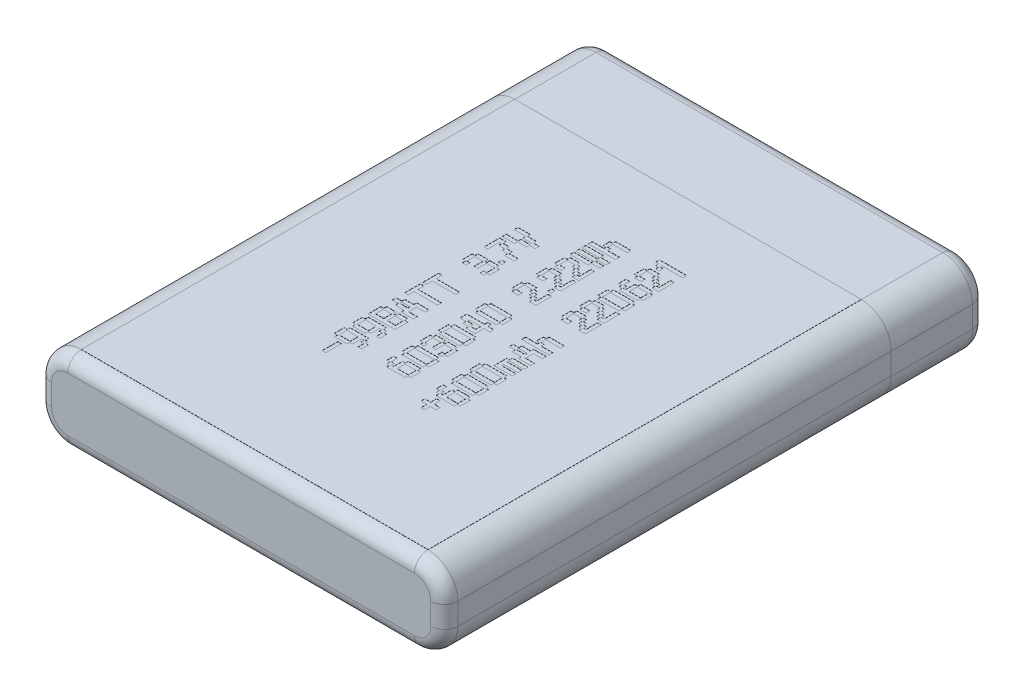
SolidWorks part; units mm, degrees
ref_plane "Front Plane" through (0, 0, 0) normal (0, 0, 1) x (1, 0, 0)
ref_plane "Top Plane" through (0, 0, 0) normal (0, 1, 0) x (1, 0, 0)
ref_plane "Right Plane" through (0, 0, 0) normal (1, 0, 0) x (0, 0, -1)
sketch "Sketch1" plane through (0, 0, 0) normal (0, 1, 0) x (1, 0, 0)
  line L1 (-15, 20) -> (15, 20)
  line L2 (-15, 20) -> (-15, -20)
  line L3 (-15, -20) -> (15, -20)
  line L4 (15, 20) -> (15, -20)
  line L5 (-15, 20) -> (15, -20) construction
  line L6 (-15, -20) -> (15, 20) construction
  point P0 (0, 0)
  dimension "D1" = 40
  dimension "D2" = 30
extrude "Boss-Extrude1" add sketch "Sketch1" along normal blind 6
sketch "Sketch2" plane through (0, 6, 0) normal (0, 1, 0) x (1, 0, 0)
  line L0 (-15, 13) -> (15, 13)
  line L1 (-15, 20) -> (-15, -20) construction
  line L2 (15, -20) -> (15, 20) construction
  line L3 (15, 20) -> (-15, 20) construction
  dimension "D1" = 7
split line "Split Line2"
sketch "Sketch3" plane through (-15, 0, 0) normal (-1, 0, 0) x (0, 0, 1)
  line L0 (-13, 6) -> (-13, 0)
  line L1 (-20, 0) -> (20, 0) construction
split line "Split Line3"
sketch "Sketch4" plane through (0, 0, 0) normal (0, -1, 0) x (-1, 0, 0)
  line L0 (15, 13) -> (-15, 13)
split line "Split Line4"
sketch "Sketch5" plane through (15, 0, 0) normal (1, 0, 0) x (0, 0, -1)
  line L0 (13, 6) -> (13, 0)
split line "Split Line5"
fillet "Fillet1" radius 2.2 8 edges at (-15, 0, -16.5) (-15, 6, -16.5) (15, 0, 3.5) (15, 0, -16.5) (15, 6, -16.5) (15, 6, 3.5) (-15, 0, 3.5) (-15, 6, 3.5)
fillet "Fillet2" radius 1 16 edges at (14.3556, 5.3556, -20) (15, 3, -20) (14.3556, 0.6444, -20) (0, 0, -20) (-14.3556, 0.6444, -20) (-15, 3, -20) (-14.3556, 5.3556, -20) (-14.3556, 5.3556, 20) (-15, 3, 20) (-14.3556, 0.6444, 20) (0, 0, 20) (14.3556, 0.6444, 20) (15, 3, 20) (14.3556, 5.3556, 20) (0, 6, -20) (0, 6, 20)
sketch "Sketch6" plane through (0, 6, 0) normal (0, 1, 0) x (1, 0, 0)
  line L0 (-3.5649, -10.1961) -> (-3.831, -10.1961)
  line L1 (-3.831, -10.1961) -> (-3.831, -9.0385)
  line L2 (-3.831, -9.0385) -> (-3.5649, -9.0385)
  line L3 (-3.5649, -9.0385) -> (-3.5649, -10.1961)
  line L4 (-3.3483, -8.8464) -> (-4.2643, -8.8464)
  line L5 (-4.2643, -8.8464) -> (-4.2643, -8.5562)
  line L6 (-4.2643, -8.5562) -> (-3.3483, -8.5562)
  line L7 (-3.3483, -8.5562) -> (-3.3483, -8.8464)
  line L8 (-3.1317, -8.6298) -> (-3.3974, -8.6298)
  line L9 (-3.3974, -8.6298) -> (-3.3974, -7.9795)
  line L10 (-3.3974, -7.9795) -> (-4.2643, -7.9795)
  line L11 (-4.2643, -7.9795) -> (-4.2643, -7.6888)
  line L12 (-4.2643, -7.6888) -> (-2.9146, -7.6888)
  line L13 (-2.9146, -7.6888) -> (-2.9146, -7.9795)
  line L14 (-2.9146, -7.9795) -> (-3.1317, -7.9795)
  line L15 (-3.1317, -7.9795) -> (-3.1317, -8.6298)
  line L16 (-2.4813, -8.6298) -> (-2.7471, -8.6298)
  line L17 (-2.7471, -8.6298) -> (-2.7471, -8.1225)
  line L18 (-2.7471, -8.1225) -> (-2.4813, -8.1225)
  line L19 (-2.4813, -8.1225) -> (-2.4813, -8.6298)
  line L20 (-4.2152, -8.6298) -> (-4.4813, -8.6298)
  line L21 (-4.4813, -8.6298) -> (-4.4813, -7.9058)
  line L22 (-4.4813, -7.9058) -> (-4.2152, -7.9058)
  line L23 (-4.2152, -7.9058) -> (-4.2152, -8.6298)
  line L24 (-2.698, -8.1961) -> (-2.9637, -8.1961)
  line L25 (-2.9637, -8.1961) -> (-2.9637, -7.9058)
  line L26 (-2.9637, -7.9058) -> (-2.698, -7.9058)
  line L27 (-2.698, -7.9058) -> (-2.698, -8.1961)
  line L28 (-3.3483, -7.4967) -> (-4.2643, -7.4967)
  line L29 (-4.2643, -7.4967) -> (-4.2643, -7.2065)
  line L30 (-4.2643, -7.2065) -> (-3.3483, -7.2065)
  line L31 (-3.3483, -7.2065) -> (-3.3483, -7.4967)
  line L32 (-3.1317, -7.2801) -> (-3.3974, -7.2801)
  line L33 (-3.3974, -7.2801) -> (-3.3974, -6.6298)
  line L34 (-3.3974, -6.6298) -> (-4.2643, -6.6298)
  line L35 (-4.2643, -6.6298) -> (-4.2643, -6.3391)
  line L36 (-4.2643, -6.3391) -> (-2.9146, -6.3391)
  line L37 (-2.9146, -6.3391) -> (-2.9146, -6.6298)
  line L38 (-2.9146, -6.6298) -> (-3.1317, -6.6298)
  line L39 (-3.1317, -6.6298) -> (-3.1317, -7.2801)
  line L40 (-2.4813, -7.2801) -> (-2.7471, -7.2801)
  line L41 (-2.7471, -7.2801) -> (-2.7471, -6.7728)
  line L42 (-2.7471, -6.7728) -> (-2.4813, -6.7728)
  line L43 (-2.4813, -6.7728) -> (-2.4813, -7.2801)
  line L44 (-4.2152, -7.2801) -> (-4.4813, -7.2801)
  line L45 (-4.4813, -7.2801) -> (-4.4813, -6.5562)
  line L46 (-4.4813, -6.5562) -> (-4.2152, -6.5562)
  line L47 (-4.2152, -6.5562) -> (-4.2152, -7.2801)
  line L48 (-2.698, -6.8464) -> (-2.9637, -6.8464)
  line L49 (-2.9637, -6.8464) -> (-2.9637, -6.5562)
  line L50 (-2.9637, -6.5562) -> (-2.698, -6.5562)
  line L51 (-2.698, -6.5562) -> (-2.698, -6.8464)
  line L52 (-2.4813, -6.147) -> (-4.4813, -6.147)
  line L53 (-4.4813, -6.147) -> (-4.4813, -5.2065)
  line L54 (-4.4813, -5.2065) -> (-4.2152, -5.2065)
  line L55 (-4.2152, -5.2065) -> (-4.2152, -5.8568)
  line L56 (-4.2152, -5.8568) -> (-3.614, -5.8568)
  line L57 (-3.614, -5.8568) -> (-3.614, -5.2065)
  line L58 (-3.614, -5.2065) -> (-3.3483, -5.2065)
  line L59 (-3.3483, -5.2065) -> (-3.3483, -5.8568)
  line L60 (-3.3483, -5.8568) -> (-2.7471, -5.8568)
  line L61 (-2.7471, -5.8568) -> (-2.7471, -5.2065)
  line L62 (-2.7471, -5.2065) -> (-2.4813, -5.2065)
  line L63 (-2.4813, -5.2065) -> (-2.4813, -6.147)
  line L64 (-2.698, -5.2801) -> (-3.3974, -5.2801)
  line L65 (-3.3974, -5.2801) -> (-3.3974, -4.9894)
  line L66 (-3.3974, -4.9894) -> (-2.698, -4.9894)
  line L67 (-2.698, -4.9894) -> (-2.698, -5.2801)
  line L68 (-3.5649, -5.2801) -> (-4.2643, -5.2801)
  line L69 (-4.2643, -5.2801) -> (-4.2643, -4.9894)
  line L70 (-4.2643, -4.9894) -> (-3.5649, -4.9894)
  line L71 (-3.5649, -4.9894) -> (-3.5649, -5.2801)
  line L72 (-2.4813, -4.7973) -> (-3.3974, -4.7973)
  line L73 (-3.3974, -4.7973) -> (-3.3974, -4.5807)
  line L74 (-3.3974, -4.5807) -> (-4.0477, -4.5807)
  line L75 (-4.0477, -4.5807) -> (-4.0477, -4.2901)
  line L76 (-4.0477, -4.2901) -> (-3.3974, -4.2901)
  line L77 (-3.3974, -4.2901) -> (-3.3974, -4.147)
  line L78 (-3.3974, -4.147) -> (-4.0477, -4.147)
  line L79 (-4.0477, -4.147) -> (-4.0477, -3.8568)
  line L80 (-4.0477, -3.8568) -> (-3.3974, -3.8568)
  line L81 (-3.3974, -3.8568) -> (-3.3974, -3.6397)
  line L82 (-3.3974, -3.6397) -> (-2.4813, -3.6397)
  line L83 (-2.4813, -3.6397) -> (-2.4813, -3.9304)
  line L84 (-2.4813, -3.9304) -> (-3.1317, -3.9304)
  line L85 (-3.1317, -3.9304) -> (-3.1317, -4.5071)
  line L86 (-3.1317, -4.5071) -> (-2.4813, -4.5071)
  line L87 (-2.4813, -4.5071) -> (-2.4813, -4.7973)
  line L88 (-3.9986, -4.3637) -> (-4.4813, -4.3637)
  line L89 (-4.4813, -4.3637) -> (-4.4813, -4.0734)
  line L90 (-4.4813, -4.0734) -> (-3.9986, -4.0734)
  line L91 (-3.9986, -4.0734) -> (-3.9986, -4.3637)
  line L92 (-4.2152, -3.4476) -> (-4.4813, -3.4476)
  line L93 (-4.4813, -3.4476) -> (-4.4813, -2.2901)
  line L94 (-4.4813, -2.2901) -> (-4.2152, -2.2901)
  line L95 (-4.2152, -2.2901) -> (-4.2152, -2.7237)
  line L96 (-4.2152, -2.7237) -> (-2.4813, -2.7237)
  line L97 (-2.4813, -2.7237) -> (-2.4813, -3.014)
  line L98 (-2.4813, -3.014) -> (-4.2152, -3.014)
  line L99 (-4.2152, -3.014) -> (-4.2152, -3.4476)
  line L100 (-4.2152, -2.0979) -> (-4.4813, -2.0979)
  line L101 (-4.4813, -2.0979) -> (-4.4813, -0.9404)
  line L102 (-4.4813, -0.9404) -> (-4.2152, -0.9404)
  line L103 (-4.2152, -0.9404) -> (-4.2152, -1.374)
  line L104 (-4.2152, -1.374) -> (-2.4813, -1.374)
  line L105 (-2.4813, -1.374) -> (-2.4813, -1.6643)
  line L106 (-2.4813, -1.6643) -> (-4.2152, -1.6643)
  line L107 (-4.2152, -1.6643) -> (-4.2152, -2.0979)
  line L108 (-2.698, 0.6014) -> (-2.9637, 0.6014)
  line L109 (-2.9637, 0.6014) -> (-2.9637, 0.8917)
  line L110 (-2.9637, 0.8917) -> (-2.698, 0.8917)
  line L111 (-2.698, 0.8917) -> (-2.698, 0.6014)
  line L112 (-3.9986, 0.6014) -> (-4.2643, 0.6014)
  line L113 (-4.2643, 0.6014) -> (-4.2643, 0.8917)
  line L114 (-4.2643, 0.8917) -> (-3.9986, 0.8917)
  line L115 (-3.9986, 0.8917) -> (-3.9986, 0.6014)
  line L116 (-2.7471, 0.8181) -> (-2.7471, 1.542)
  line L117 (-2.7471, 1.542) -> (-2.4813, 1.542)
  line L118 (-2.4813, 1.542) -> (-2.4813, 0.8181)
  line L119 (-2.4813, 0.8181) -> (-2.7471, 0.8181)
  line L120 (-3.3483, 0.8181) -> (-3.614, 0.8181)
  line L121 (-3.614, 0.8181) -> (-3.614, 1.542)
  line L122 (-3.614, 1.542) -> (-3.3483, 1.542)
  line L123 (-3.3483, 1.542) -> (-3.3483, 0.8181)
  line L124 (-4.2152, 0.8181) -> (-4.4813, 0.8181)
  line L125 (-4.4813, 0.8181) -> (-4.4813, 1.542)
  line L126 (-4.4813, 1.542) -> (-4.2152, 1.542)
  line L127 (-4.2152, 1.542) -> (-4.2152, 0.8181)
  line L128 (-2.698, 1.4684) -> (-3.3974, 1.4684)
  line L129 (-3.3974, 1.4684) -> (-3.3974, 1.759)
  line L130 (-3.3974, 1.759) -> (-2.698, 1.759)
  line L131 (-2.698, 1.759) -> (-2.698, 1.4684)
  line L132 (-3.5649, 1.4684) -> (-4.2643, 1.4684)
  line L133 (-4.2643, 1.4684) -> (-4.2643, 1.759)
  line L134 (-4.2643, 1.759) -> (-3.5649, 1.759)
  line L135 (-3.5649, 1.759) -> (-3.5649, 1.4684)
  line L136 (-2.698, 1.9511) -> (-2.9637, 1.9511)
  line L137 (-2.9637, 1.9511) -> (-2.9637, 2.2414)
  line L138 (-2.9637, 2.2414) -> (-2.698, 2.2414)
  line L139 (-2.698, 2.2414) -> (-2.698, 1.9511)
  line L140 (-4.2152, 2.4174) -> (-4.4813, 2.4174)
  line L141 (-4.4813, 2.4174) -> (-4.4813, 3.575)
  line L142 (-4.4813, 3.575) -> (-3.9986, 3.575)
  line L143 (-3.9986, 3.575) -> (-3.9986, 3.2843)
  line L144 (-3.9986, 3.2843) -> (-4.2152, 3.2843)
  line L145 (-4.2152, 3.2843) -> (-4.2152, 2.4174)
  line L146 (-3.1807, 2.634) -> (-3.1807, 2.9247)
  line L147 (-3.1807, 2.9247) -> (-2.4813, 2.9247)
  line L148 (-2.4813, 2.9247) -> (-2.4813, 2.634)
  line L149 (-2.4813, 2.634) -> (-3.1807, 2.634)
  line L150 (-3.1317, 2.8511) -> (-3.614, 2.8511)
  line L151 (-3.614, 2.8511) -> (-3.614, 3.1413)
  line L152 (-3.614, 3.1413) -> (-3.1317, 3.1413)
  line L153 (-3.1317, 3.1413) -> (-3.1317, 2.8511)
  line L154 (-3.5649, 3.0677) -> (-4.0477, 3.0677)
  line L155 (-4.0477, 3.0677) -> (-4.0477, 3.358)
  line L156 (-4.0477, 3.358) -> (-3.5649, 3.358)
  line L157 (-3.5649, 3.358) -> (-3.5649, 3.0677)
  line L158 (-3.5649, 3.7671) -> (-4.4813, 3.7671)
  line L159 (-4.4813, 3.7671) -> (-4.4813, 4.0573)
  line L160 (-4.4813, 4.0573) -> (-3.5649, 4.0573)
  line L161 (-3.5649, 4.0573) -> (-3.5649, 3.7671)
  line L162 (-2.9146, 3.9837) -> (-3.614, 3.9837)
  line L163 (-3.614, 3.9837) -> (-3.614, 4.2744)
  line L164 (-3.614, 4.2744) -> (-2.9146, 4.2744)
  line L165 (-2.9146, 4.2744) -> (-2.9146, 3.9837)
  line L166 (-2.9637, 4.2007) -> (-2.9637, 4.491)
  line L167 (-2.9637, 4.491) -> (-2.4813, 4.491)
  line L168 (-2.4813, 4.491) -> (-2.4813, 4.2007)
  line L169 (-2.4813, 4.2007) -> (-2.9637, 4.2007)
  line L170 (-2.9146, 4.4174) -> (-3.614, 4.4174)
  line L171 (-3.614, 4.4174) -> (-3.614, 4.7076)
  line L172 (-3.614, 4.7076) -> (-2.9146, 4.7076)
  line L173 (-2.9146, 4.7076) -> (-2.9146, 4.4174)
  line L174 (-3.5649, 4.634) -> (-4.4813, 4.634)
  line L175 (-4.4813, 4.634) -> (-4.4813, 4.9247)
  line L176 (-4.4813, 4.9247) -> (-3.5649, 4.9247)
  line L177 (-3.5649, 4.9247) -> (-3.5649, 4.634)
  line L178 (0.9523, -8.8464) -> (-0.3974, -8.8464)
  line L179 (-0.3974, -8.8464) -> (-0.3974, -8.5562)
  line L180 (-0.3974, -8.5562) -> (-0.1807, -8.5562)
  line L181 (-0.1807, -8.5562) -> (-0.1807, -7.9058)
  line L182 (-0.1807, -7.9058) -> (0.0854, -7.9058)
  line L183 (0.0854, -7.9058) -> (0.0854, -8.5562)
  line L184 (0.0854, -8.5562) -> (0.9523, -8.5562)
  line L185 (0.9523, -8.5562) -> (0.9523, -8.8464)
  line L186 (0.9032, -8.6298) -> (0.9032, -7.9058)
  line L187 (0.9032, -7.9058) -> (1.169, -7.9058)
  line L188 (1.169, -7.9058) -> (1.169, -8.6298)
  line L189 (1.169, -8.6298) -> (0.9032, -8.6298)
  line L190 (-0.3483, -8.6298) -> (-0.614, -8.6298)
  line L191 (-0.614, -8.6298) -> (-0.614, -8.3391)
  line L192 (-0.614, -8.3391) -> (-0.3483, -8.3391)
  line L193 (-0.3483, -8.3391) -> (-0.3483, -8.6298)
  line L194 (-0.5649, -8.4128) -> (-0.831, -8.4128)
  line L195 (-0.831, -8.4128) -> (-0.831, -7.9058)
  line L196 (-0.831, -7.9058) -> (-0.5649, -7.9058)
  line L197 (-0.5649, -7.9058) -> (-0.5649, -8.4128)
  line L198 (0.9523, -7.9795) -> (0.0363, -7.9795)
  line L199 (0.0363, -7.9795) -> (0.0363, -7.6888)
  line L200 (0.0363, -7.6888) -> (0.9523, -7.6888)
  line L201 (0.9523, -7.6888) -> (0.9523, -7.9795)
  line L202 (0.9523, -7.4967) -> (-0.614, -7.4967)
  line L203 (-0.614, -7.4967) -> (-0.614, -7.2065)
  line L204 (-0.614, -7.2065) -> (0.9523, -7.2065)
  line L205 (0.9523, -7.2065) -> (0.9523, -7.4967)
  line L206 (0.9032, -6.5562) -> (1.169, -6.5562)
  line L207 (1.169, -6.5562) -> (1.169, -7.2801)
  line L208 (1.169, -7.2801) -> (0.9032, -7.2801)
  line L209 (0.9032, -7.2801) -> (0.9032, -6.5562)
  line L210 (-0.614, -6.6298) -> (-0.614, -6.3391)
  line L211 (-0.614, -6.3391) -> (0.9523, -6.3391)
  line L212 (0.9523, -6.3391) -> (0.9523, -6.6298)
  line L213 (0.9523, -6.6298) -> (-0.614, -6.6298)
  line L214 (-0.831, -6.5562) -> (-0.5649, -6.5562)
  line L215 (-0.5649, -6.5562) -> (-0.5649, -7.2801)
  line L216 (-0.5649, -7.2801) -> (-0.831, -7.2801)
  line L217 (-0.831, -7.2801) -> (-0.831, -6.5562)
  line L218 (0.9523, -6.147) -> (0.6866, -6.147)
  line L219 (0.6866, -6.147) -> (0.6866, -5.8568)
  line L220 (0.6866, -5.8568) -> (0.9523, -5.8568)
  line L221 (0.9523, -5.8568) -> (0.9523, -6.147)
  line L222 (-0.3483, -6.147) -> (-0.614, -6.147)
  line L223 (-0.614, -6.147) -> (-0.614, -5.8568)
  line L224 (-0.614, -5.8568) -> (-0.3483, -5.8568)
  line L225 (-0.3483, -5.8568) -> (-0.3483, -6.147)
  line L226 (0.9032, -5.9304) -> (0.9032, -5.2065)
  line L227 (0.9032, -5.2065) -> (1.169, -5.2065)
  line L228 (1.169, -5.2065) -> (1.169, -5.9304)
  line L229 (1.169, -5.9304) -> (0.9032, -5.9304)
  line L230 (0.302, -5.9304) -> (0.0363, -5.9304)
  line L231 (0.0363, -5.9304) -> (0.0363, -5.2065)
  line L232 (0.0363, -5.2065) -> (0.302, -5.2065)
  line L233 (0.302, -5.2065) -> (0.302, -5.9304)
  line L234 (-0.5649, -5.9304) -> (-0.831, -5.9304)
  line L235 (-0.831, -5.9304) -> (-0.831, -5.2065)
  line L236 (-0.831, -5.2065) -> (-0.5649, -5.2065)
  line L237 (-0.5649, -5.2065) -> (-0.5649, -5.9304)
  line L238 (0.9523, -5.2801) -> (0.2529, -5.2801)
  line L239 (0.2529, -5.2801) -> (0.2529, -4.9894)
  line L240 (0.2529, -4.9894) -> (0.9523, -4.9894)
  line L241 (0.9523, -4.9894) -> (0.9523, -5.2801)
  line L242 (0.0854, -5.2801) -> (-0.614, -5.2801)
  line L243 (-0.614, -5.2801) -> (-0.614, -4.9894)
  line L244 (-0.614, -4.9894) -> (0.0854, -4.9894)
  line L245 (0.0854, -4.9894) -> (0.0854, -5.2801)
  line L246 (0.9523, -4.7973) -> (-0.614, -4.7973)
  line L247 (-0.614, -4.7973) -> (-0.614, -4.5071)
  line L248 (-0.614, -4.5071) -> (0.9523, -4.5071)
  line L249 (0.9523, -4.5071) -> (0.9523, -4.7973)
  line L250 (0.9032, -3.8568) -> (1.169, -3.8568)
  line L251 (1.169, -3.8568) -> (1.169, -4.5807)
  line L252 (1.169, -4.5807) -> (0.9032, -4.5807)
  line L253 (0.9032, -4.5807) -> (0.9032, -3.8568)
  line L254 (-0.614, -3.9304) -> (-0.614, -3.6397)
  line L255 (-0.614, -3.6397) -> (0.9523, -3.6397)
  line L256 (0.9523, -3.6397) -> (0.9523, -3.9304)
  line L257 (0.9523, -3.9304) -> (-0.614, -3.9304)
  line L258 (-0.831, -3.8568) -> (-0.5649, -3.8568)
  line L259 (-0.5649, -3.8568) -> (-0.5649, -4.5807)
  line L260 (-0.5649, -4.5807) -> (-0.831, -4.5807)
  line L261 (-0.831, -4.5807) -> (-0.831, -3.8568)
  line L262 (0.7357, -3.4476) -> (0.0363, -3.4476)
  line L263 (0.0363, -3.4476) -> (0.0363, -3.1574)
  line L264 (0.0363, -3.1574) -> (0.4696, -3.1574)
  line L265 (0.4696, -3.1574) -> (0.4696, -2.7973)
  line L266 (0.4696, -2.7973) -> (-0.3483, -2.7973)
  line L267 (-0.3483, -2.7973) -> (-0.3483, -3.014)
  line L268 (-0.3483, -3.014) -> (-0.831, -3.014)
  line L269 (-0.831, -3.014) -> (-0.831, -2.5071)
  line L270 (-0.831, -2.5071) -> (0.4696, -2.5071)
  line L271 (0.4696, -2.5071) -> (0.4696, -2.2901)
  line L272 (0.4696, -2.2901) -> (0.7357, -2.2901)
  line L273 (0.7357, -2.2901) -> (0.7357, -2.5071)
  line L274 (0.7357, -2.5071) -> (1.169, -2.5071)
  line L275 (1.169, -2.5071) -> (1.169, -2.7973)
  line L276 (1.169, -2.7973) -> (0.7357, -2.7973)
  line L277 (0.7357, -2.7973) -> (0.7357, -3.4476)
  line L278 (0.0854, -3.231) -> (-0.3974, -3.231)
  line L279 (-0.3974, -3.231) -> (-0.3974, -2.9404)
  line L280 (-0.3974, -2.9404) -> (0.0854, -2.9404)
  line L281 (0.0854, -2.9404) -> (0.0854, -3.231)
  line L282 (0.9523, -2.0979) -> (-0.614, -2.0979)
  line L283 (-0.614, -2.0979) -> (-0.614, -1.8077)
  line L284 (-0.614, -1.8077) -> (0.9523, -1.8077)
  line L285 (0.9523, -1.8077) -> (0.9523, -2.0979)
  line L286 (0.9032, -1.1574) -> (1.169, -1.1574)
  line L287 (1.169, -1.1574) -> (1.169, -1.8813)
  line L288 (1.169, -1.8813) -> (0.9032, -1.8813)
  line L289 (0.9032, -1.8813) -> (0.9032, -1.1574)
  line L290 (-0.614, -1.231) -> (-0.614, -0.9404)
  line L291 (-0.614, -0.9404) -> (0.9523, -0.9404)
  line L292 (0.9523, -0.9404) -> (0.9523, -1.231)
  line L293 (0.9523, -1.231) -> (-0.614, -1.231)
  line L294 (-0.831, -1.1574) -> (-0.5649, -1.1574)
  line L295 (-0.5649, -1.1574) -> (-0.5649, -1.8813)
  line L296 (-0.5649, -1.8813) -> (-0.831, -1.8813)
  line L297 (-0.831, -1.8813) -> (-0.831, -1.1574)
  line L298 (0.6866, 0.6014) -> (0.6866, 0.8917)
  line L299 (0.6866, 0.8917) -> (0.9032, 0.8917)
  line L300 (0.9032, 0.8917) -> (0.9032, 1.759)
  line L301 (0.9032, 1.759) -> (1.169, 1.759)
  line L302 (1.169, 1.759) -> (1.169, 0.6014)
  line L303 (1.169, 0.6014) -> (0.6866, 0.6014)
  line L304 (-0.1317, 0.6014) -> (-0.614, 0.6014)
  line L305 (-0.614, 0.6014) -> (-0.614, 0.8917)
  line L306 (-0.614, 0.8917) -> (-0.1317, 0.8917)
  line L307 (-0.1317, 0.8917) -> (-0.1317, 0.6014)
  line L308 (0.7357, 0.8181) -> (0.4696, 0.8181)
  line L309 (0.4696, 0.8181) -> (0.4696, 1.1087)
  line L310 (0.4696, 1.1087) -> (0.7357, 1.1087)
  line L311 (0.7357, 1.1087) -> (0.7357, 0.8181)
  line L312 (-0.5649, 0.8181) -> (-0.831, 0.8181)
  line L313 (-0.831, 0.8181) -> (-0.831, 1.542)
  line L314 (-0.831, 1.542) -> (-0.5649, 1.542)
  line L315 (-0.5649, 1.542) -> (-0.5649, 0.8181)
  line L316 (0.5187, 1.0351) -> (0.2529, 1.0351)
  line L317 (0.2529, 1.0351) -> (0.2529, 1.3254)
  line L318 (0.2529, 1.3254) -> (0.5187, 1.3254)
  line L319 (0.5187, 1.3254) -> (0.5187, 1.0351)
  line L320 (0.302, 1.2517) -> (0.0363, 1.2517)
  line L321 (0.0363, 1.2517) -> (0.0363, 1.542)
  line L322 (0.0363, 1.542) -> (0.302, 1.542)
  line L323 (0.302, 1.542) -> (0.302, 1.2517)
  line L324 (0.0854, 1.4684) -> (-0.614, 1.4684)
  line L325 (-0.614, 1.4684) -> (-0.614, 1.759)
  line L326 (-0.614, 1.759) -> (0.0854, 1.759)
  line L327 (0.0854, 1.759) -> (0.0854, 1.4684)
  line L328 (0.9523, 1.9511) -> (0.6866, 1.9511)
  line L329 (0.6866, 1.9511) -> (0.6866, 2.2414)
  line L330 (0.6866, 2.2414) -> (0.9523, 2.2414)
  line L331 (0.9523, 2.2414) -> (0.9523, 1.9511)
  line L332 (0.6866, 2.4174) -> (0.6866, 2.7076)
  line L333 (0.6866, 2.7076) -> (0.9032, 2.7076)
  line L334 (0.9032, 2.7076) -> (0.9032, 3.575)
  line L335 (0.9032, 3.575) -> (1.169, 3.575)
  line L336 (1.169, 3.575) -> (1.169, 2.4174)
  line L337 (1.169, 2.4174) -> (0.6866, 2.4174)
  line L338 (-0.1317, 2.4174) -> (-0.614, 2.4174)
  line L339 (-0.614, 2.4174) -> (-0.614, 2.7076)
  line L340 (-0.614, 2.7076) -> (-0.1317, 2.7076)
  line L341 (-0.1317, 2.7076) -> (-0.1317, 2.4174)
  line L342 (0.7357, 2.634) -> (0.4696, 2.634)
  line L343 (0.4696, 2.634) -> (0.4696, 2.9247)
  line L344 (0.4696, 2.9247) -> (0.7357, 2.9247)
  line L345 (0.7357, 2.9247) -> (0.7357, 2.634)
  line L346 (-0.5649, 2.634) -> (-0.831, 2.634)
  line L347 (-0.831, 2.634) -> (-0.831, 3.358)
  line L348 (-0.831, 3.358) -> (-0.5649, 3.358)
  line L349 (-0.5649, 3.358) -> (-0.5649, 2.634)
  line L350 (0.5187, 2.8511) -> (0.2529, 2.8511)
  line L351 (0.2529, 2.8511) -> (0.2529, 3.1413)
  line L352 (0.2529, 3.1413) -> (0.5187, 3.1413)
  line L353 (0.5187, 3.1413) -> (0.5187, 2.8511)
  line L354 (0.302, 3.0677) -> (0.0363, 3.0677)
  line L355 (0.0363, 3.0677) -> (0.0363, 3.358)
  line L356 (0.0363, 3.358) -> (0.302, 3.358)
  line L357 (0.302, 3.358) -> (0.302, 3.0677)
  line L358 (0.0854, 3.2843) -> (-0.614, 3.2843)
  line L359 (-0.614, 3.2843) -> (-0.614, 3.575)
  line L360 (-0.614, 3.575) -> (0.0854, 3.575)
  line L361 (0.0854, 3.575) -> (0.0854, 3.2843)
  line L362 (0.6866, 3.7671) -> (0.6866, 4.0573)
  line L363 (0.6866, 4.0573) -> (0.9032, 4.0573)
  line L364 (0.9032, 4.0573) -> (0.9032, 4.9247)
  line L365 (0.9032, 4.9247) -> (1.169, 4.9247)
  line L366 (1.169, 4.9247) -> (1.169, 3.7671)
  line L367 (1.169, 3.7671) -> (0.6866, 3.7671)
  line L368 (-0.1317, 3.7671) -> (-0.614, 3.7671)
  line L369 (-0.614, 3.7671) -> (-0.614, 4.0573)
  line L370 (-0.614, 4.0573) -> (-0.1317, 4.0573)
  line L371 (-0.1317, 4.0573) -> (-0.1317, 3.7671)
  line L372 (0.7357, 3.9837) -> (0.4696, 3.9837)
  line L373 (0.4696, 3.9837) -> (0.4696, 4.2744)
  line L374 (0.4696, 4.2744) -> (0.7357, 4.2744)
  line L375 (0.7357, 4.2744) -> (0.7357, 3.9837)
  line L376 (-0.5649, 3.9837) -> (-0.831, 3.9837)
  line L377 (-0.831, 3.9837) -> (-0.831, 4.7076)
  line L378 (-0.831, 4.7076) -> (-0.5649, 4.7076)
  line L379 (-0.5649, 4.7076) -> (-0.5649, 3.9837)
  line L380 (0.5187, 4.2007) -> (0.2529, 4.2007)
  line L381 (0.2529, 4.2007) -> (0.2529, 4.491)
  line L382 (0.2529, 4.491) -> (0.5187, 4.491)
  line L383 (0.5187, 4.491) -> (0.5187, 4.2007)
  line L384 (0.302, 4.4174) -> (0.0363, 4.4174)
  line L385 (0.0363, 4.4174) -> (0.0363, 4.7076)
  line L386 (0.0363, 4.7076) -> (0.302, 4.7076)
  line L387 (0.302, 4.7076) -> (0.302, 4.4174)
  line L388 (0.0854, 4.634) -> (-0.614, 4.634)
  line L389 (-0.614, 4.634) -> (-0.614, 4.9247)
  line L390 (-0.614, 4.9247) -> (0.0854, 4.9247)
  line L391 (0.0854, 4.9247) -> (0.0854, 4.634)
  line L392 (0.5187, 5.1168) -> (-0.831, 5.1168)
  line L393 (-0.831, 5.1168) -> (-0.831, 5.407)
  line L394 (-0.831, 5.407) -> (0.5187, 5.407)
  line L395 (0.5187, 5.407) -> (0.5187, 5.1168)
  line L396 (0.4696, 5.3334) -> (0.4696, 5.6241)
  line L397 (0.4696, 5.6241) -> (1.169, 5.6241)
  line L398 (1.169, 5.6241) -> (1.169, 5.3334)
  line L399 (1.169, 5.3334) -> (0.4696, 5.3334)
  line L400 (0.5187, 5.5504) -> (-0.831, 5.5504)
  line L401 (-0.831, 5.5504) -> (-0.831, 5.8407)
  line L402 (-0.831, 5.8407) -> (0.5187, 5.8407)
  line L403 (0.5187, 5.8407) -> (0.5187, 5.5504)
  line L404 (0.4696, 5.7671) -> (0.4696, 6.0573)
  line L405 (0.4696, 6.0573) -> (1.169, 6.0573)
  line L406 (1.169, 6.0573) -> (1.169, 5.7671)
  line L407 (1.169, 5.7671) -> (0.4696, 5.7671)
  line L408 (0.5187, 5.9837) -> (-0.831, 5.9837)
  line L409 (-0.831, 5.9837) -> (-0.831, 6.2744)
  line L410 (-0.831, 6.2744) -> (0.5187, 6.2744)
  line L411 (0.5187, 6.2744) -> (0.5187, 5.9837)
  line L412 (1.169, 6.4665) -> (-0.831, 6.4665)
  line L413 (-0.831, 6.4665) -> (-0.831, 6.7567)
  line L414 (-0.831, 6.7567) -> (0.0363, 6.7567)
  line L415 (0.0363, 6.7567) -> (0.0363, 6.9738)
  line L416 (0.0363, 6.9738) -> (0.302, 6.9738)
  line L417 (0.302, 6.9738) -> (0.302, 6.7567)
  line L418 (0.302, 6.7567) -> (1.169, 6.7567)
  line L419 (1.169, 6.7567) -> (1.169, 6.4665)
  line L420 (0.0854, 6.9001) -> (-0.1807, 6.9001)
  line L421 (-0.1807, 6.9001) -> (-0.1807, 7.407)
  line L422 (-0.1807, 7.407) -> (0.0854, 7.407)
  line L423 (0.0854, 7.407) -> (0.0854, 6.9001)
  line L424 (1.169, 7.3334) -> (0.0363, 7.3334)
  line L425 (0.0363, 7.3334) -> (0.0363, 7.6241)
  line L426 (0.0363, 7.6241) -> (1.169, 7.6241)
  line L427 (1.169, 7.6241) -> (1.169, 7.3334)
  line L428 (3.7357, -10.1961) -> (3.4696, -10.1961)
  line L429 (3.4696, -10.1961) -> (3.4696, -9.7624)
  line L430 (3.4696, -9.7624) -> (3.0363, -9.7624)
  line L431 (3.0363, -9.7624) -> (3.0363, -9.4722)
  line L432 (3.0363, -9.4722) -> (3.4696, -9.4722)
  line L433 (3.4696, -9.4722) -> (3.4696, -9.0385)
  line L434 (3.4696, -9.0385) -> (3.7357, -9.0385)
  line L435 (3.7357, -9.0385) -> (3.7357, -9.4722)
  line L436 (3.7357, -9.4722) -> (4.169, -9.4722)
  line L437 (4.169, -9.4722) -> (4.169, -9.7624)
  line L438 (4.169, -9.7624) -> (3.7357, -9.7624)
  line L439 (3.7357, -9.7624) -> (3.7357, -10.1961)
  line L440 (4.6026, -8.8464) -> (3.2529, -8.8464)
  line L441 (3.2529, -8.8464) -> (3.2529, -8.5562)
  line L442 (3.2529, -8.5562) -> (3.4696, -8.5562)
  line L443 (3.4696, -8.5562) -> (3.4696, -7.9058)
  line L444 (3.4696, -7.9058) -> (3.7357, -7.9058)
  line L445 (3.7357, -7.9058) -> (3.7357, -8.5562)
  line L446 (3.7357, -8.5562) -> (4.6026, -8.5562)
  line L447 (4.6026, -8.5562) -> (4.6026, -8.8464)
  line L448 (4.5535, -8.6298) -> (4.5535, -7.9058)
  line L449 (4.5535, -7.9058) -> (4.8193, -7.9058)
  line L450 (4.8193, -7.9058) -> (4.8193, -8.6298)
  line L451 (4.8193, -8.6298) -> (4.5535, -8.6298)
  line L452 (3.302, -8.6298) -> (3.0363, -8.6298)
  line L453 (3.0363, -8.6298) -> (3.0363, -8.3391)
  line L454 (3.0363, -8.3391) -> (3.302, -8.3391)
  line L455 (3.302, -8.3391) -> (3.302, -8.6298)
  line L456 (3.0854, -8.4128) -> (2.8193, -8.4128)
  line L457 (2.8193, -8.4128) -> (2.8193, -7.9058)
  line L458 (2.8193, -7.9058) -> (3.0854, -7.9058)
  line L459 (3.0854, -7.9058) -> (3.0854, -8.4128)
  line L460 (4.6026, -7.9795) -> (3.6866, -7.9795)
  line L461 (3.6866, -7.9795) -> (3.6866, -7.6888)
  line L462 (3.6866, -7.6888) -> (4.6026, -7.6888)
  line L463 (4.6026, -7.6888) -> (4.6026, -7.9795)
  line L464 (4.6026, -7.4967) -> (3.0363, -7.4967)
  line L465 (3.0363, -7.4967) -> (3.0363, -7.2065)
  line L466 (3.0363, -7.2065) -> (4.6026, -7.2065)
  line L467 (4.6026, -7.2065) -> (4.6026, -7.4967)
  line L468 (4.5535, -6.5562) -> (4.8193, -6.5562)
  line L469 (4.8193, -6.5562) -> (4.8193, -7.2801)
  line L470 (4.8193, -7.2801) -> (4.5535, -7.2801)
  line L471 (4.5535, -7.2801) -> (4.5535, -6.5562)
  line L472 (3.0363, -6.6298) -> (3.0363, -6.3391)
  line L473 (3.0363, -6.3391) -> (4.6026, -6.3391)
  line L474 (4.6026, -6.3391) -> (4.6026, -6.6298)
  line L475 (4.6026, -6.6298) -> (3.0363, -6.6298)
  line L476 (2.8193, -6.5562) -> (3.0854, -6.5562)
  line L477 (3.0854, -6.5562) -> (3.0854, -7.2801)
  line L478 (3.0854, -7.2801) -> (2.8193, -7.2801)
  line L479 (2.8193, -7.2801) -> (2.8193, -6.5562)
  line L480 (4.6026, -6.147) -> (3.0363, -6.147)
  line L481 (3.0363, -6.147) -> (3.0363, -5.8568)
  line L482 (3.0363, -5.8568) -> (4.6026, -5.8568)
  line L483 (4.6026, -5.8568) -> (4.6026, -6.147)
  line L484 (4.5535, -5.2065) -> (4.8193, -5.2065)
  line L485 (4.8193, -5.2065) -> (4.8193, -5.9304)
  line L486 (4.8193, -5.9304) -> (4.5535, -5.9304)
  line L487 (4.5535, -5.9304) -> (4.5535, -5.2065)
  line L488 (3.0363, -5.2801) -> (3.0363, -4.9894)
  line L489 (3.0363, -4.9894) -> (4.6026, -4.9894)
  line L490 (4.6026, -4.9894) -> (4.6026, -5.2801)
  line L491 (4.6026, -5.2801) -> (3.0363, -5.2801)
  line L492 (2.8193, -5.2065) -> (3.0854, -5.2065)
  line L493 (3.0854, -5.2065) -> (3.0854, -5.9304)
  line L494 (3.0854, -5.9304) -> (2.8193, -5.9304)
  line L495 (2.8193, -5.9304) -> (2.8193, -5.2065)
  line L496 (4.8193, -4.7973) -> (3.4696, -4.7973)
  line L497 (3.4696, -4.7973) -> (3.4696, -3.8568)
  line L498 (3.4696, -3.8568) -> (3.7357, -3.8568)
  line L499 (3.7357, -3.8568) -> (3.7357, -4.0734)
  line L500 (3.7357, -4.0734) -> (4.8193, -4.0734)
  line L501 (4.8193, -4.0734) -> (4.8193, -4.3637)
  line L502 (4.8193, -4.3637) -> (3.7357, -4.3637)
  line L503 (3.7357, -4.3637) -> (3.7357, -4.5071)
  line L504 (3.7357, -4.5071) -> (4.8193, -4.5071)
  line L505 (4.8193, -4.5071) -> (4.8193, -4.7973)
  line L506 (4.8193, -3.9304) -> (3.6866, -3.9304)
  line L507 (3.6866, -3.9304) -> (3.6866, -3.6397)
  line L508 (3.6866, -3.6397) -> (4.8193, -3.6397)
  line L509 (4.8193, -3.6397) -> (4.8193, -3.9304)
  line L510 (4.8193, -3.4476) -> (3.9032, -3.4476)
  line L511 (3.9032, -3.4476) -> (3.9032, -3.231)
  line L512 (3.9032, -3.231) -> (3.2529, -3.231)
  line L513 (3.2529, -3.231) -> (3.2529, -2.9404)
  line L514 (3.2529, -2.9404) -> (3.9032, -2.9404)
  line L515 (3.9032, -2.9404) -> (3.9032, -2.7973)
  line L516 (3.9032, -2.7973) -> (3.2529, -2.7973)
  line L517 (3.2529, -2.7973) -> (3.2529, -2.5071)
  line L518 (3.2529, -2.5071) -> (3.9032, -2.5071)
  line L519 (3.9032, -2.5071) -> (3.9032, -2.2901)
  line L520 (3.9032, -2.2901) -> (4.8193, -2.2901)
  line L521 (4.8193, -2.2901) -> (4.8193, -2.5807)
  line L522 (4.8193, -2.5807) -> (4.169, -2.5807)
  line L523 (4.169, -2.5807) -> (4.169, -3.1574)
  line L524 (4.169, -3.1574) -> (4.8193, -3.1574)
  line L525 (4.8193, -3.1574) -> (4.8193, -3.4476)
  line L526 (3.302, -3.014) -> (2.8193, -3.014)
  line L527 (2.8193, -3.014) -> (2.8193, -2.7237)
  line L528 (2.8193, -2.7237) -> (3.302, -2.7237)
  line L529 (3.302, -2.7237) -> (3.302, -3.014)
  line L530 (4.8193, -2.0979) -> (2.8193, -2.0979)
  line L531 (2.8193, -2.0979) -> (2.8193, -1.8077)
  line L532 (2.8193, -1.8077) -> (3.6866, -1.8077)
  line L533 (3.6866, -1.8077) -> (3.6866, -1.5907)
  line L534 (3.6866, -1.5907) -> (3.9523, -1.5907)
  line L535 (3.9523, -1.5907) -> (3.9523, -1.8077)
  line L536 (3.9523, -1.8077) -> (4.8193, -1.8077)
  line L537 (4.8193, -1.8077) -> (4.8193, -2.0979)
  line L538 (3.7357, -1.6643) -> (3.4696, -1.6643)
  line L539 (3.4696, -1.6643) -> (3.4696, -1.1574)
  line L540 (3.4696, -1.1574) -> (3.7357, -1.1574)
  line L541 (3.7357, -1.1574) -> (3.7357, -1.6643)
  line L542 (4.8193, -1.231) -> (3.6866, -1.231)
  line L543 (3.6866, -1.231) -> (3.6866, -0.9404)
  line L544 (3.6866, -0.9404) -> (4.8193, -0.9404)
  line L545 (4.8193, -0.9404) -> (4.8193, -1.231)
  line L546 (4.3369, 0.6014) -> (4.3369, 0.8917)
  line L547 (4.3369, 0.8917) -> (4.5535, 0.8917)
  line L548 (4.5535, 0.8917) -> (4.5535, 1.759)
  line L549 (4.5535, 1.759) -> (4.8193, 1.759)
  line L550 (4.8193, 1.759) -> (4.8193, 0.6014)
  line L551 (4.8193, 0.6014) -> (4.3369, 0.6014)
  line L552 (3.5187, 0.6014) -> (3.0363, 0.6014)
  line L553 (3.0363, 0.6014) -> (3.0363, 0.8917)
  line L554 (3.0363, 0.8917) -> (3.5187, 0.8917)
  line L555 (3.5187, 0.8917) -> (3.5187, 0.6014)
  line L556 (4.386, 0.8181) -> (4.1199, 0.8181)
  line L557 (4.1199, 0.8181) -> (4.1199, 1.1087)
  line L558 (4.1199, 1.1087) -> (4.386, 1.1087)
  line L559 (4.386, 1.1087) -> (4.386, 0.8181)
  line L560 (3.0854, 0.8181) -> (2.8193, 0.8181)
  line L561 (2.8193, 0.8181) -> (2.8193, 1.542)
  line L562 (2.8193, 1.542) -> (3.0854, 1.542)
  line L563 (3.0854, 1.542) -> (3.0854, 0.8181)
  line L564 (4.169, 1.0351) -> (3.9032, 1.0351)
  line L565 (3.9032, 1.0351) -> (3.9032, 1.3254)
  line L566 (3.9032, 1.3254) -> (4.169, 1.3254)
  line L567 (4.169, 1.3254) -> (4.169, 1.0351)
  line L568 (3.9523, 1.2517) -> (3.6866, 1.2517)
  line L569 (3.6866, 1.2517) -> (3.6866, 1.542)
  line L570 (3.6866, 1.542) -> (3.9523, 1.542)
  line L571 (3.9523, 1.542) -> (3.9523, 1.2517)
  line L572 (3.7357, 1.4684) -> (3.0363, 1.4684)
  line L573 (3.0363, 1.4684) -> (3.0363, 1.759)
  line L574 (3.0363, 1.759) -> (3.7357, 1.759)
  line L575 (3.7357, 1.759) -> (3.7357, 1.4684)
  line L576 (4.3369, 1.9511) -> (4.3369, 2.2414)
  line L577 (4.3369, 2.2414) -> (4.5535, 2.2414)
  line L578 (4.5535, 2.2414) -> (4.5535, 3.1087)
  line L579 (4.5535, 3.1087) -> (4.8193, 3.1087)
  line L580 (4.8193, 3.1087) -> (4.8193, 1.9511)
  line L581 (4.8193, 1.9511) -> (4.3369, 1.9511)
  line L582 (3.5187, 1.9511) -> (3.0363, 1.9511)
  line L583 (3.0363, 1.9511) -> (3.0363, 2.2414)
  line L584 (3.0363, 2.2414) -> (3.5187, 2.2414)
  line L585 (3.5187, 2.2414) -> (3.5187, 1.9511)
  line L586 (4.386, 2.1678) -> (4.1199, 2.1678)
  line L587 (4.1199, 2.1678) -> (4.1199, 2.4584)
  line L588 (4.1199, 2.4584) -> (4.386, 2.4584)
  line L589 (4.386, 2.4584) -> (4.386, 2.1678)
  line L590 (3.0854, 2.1678) -> (2.8193, 2.1678)
  line L591 (2.8193, 2.1678) -> (2.8193, 2.8917)
  line L592 (2.8193, 2.8917) -> (3.0854, 2.8917)
  line L593 (3.0854, 2.8917) -> (3.0854, 2.1678)
  line L594 (4.169, 2.3848) -> (3.9032, 2.3848)
  line L595 (3.9032, 2.3848) -> (3.9032, 2.6751)
  line L596 (3.9032, 2.6751) -> (4.169, 2.6751)
  line L597 (4.169, 2.6751) -> (4.169, 2.3848)
  line L598 (3.9523, 2.6014) -> (3.6866, 2.6014)
  line L599 (3.6866, 2.6014) -> (3.6866, 2.8917)
  line L600 (3.6866, 2.8917) -> (3.9523, 2.8917)
  line L601 (3.9523, 2.8917) -> (3.9523, 2.6014)
  line L602 (3.7357, 2.8181) -> (3.0363, 2.8181)
  line L603 (3.0363, 2.8181) -> (3.0363, 3.1087)
  line L604 (3.0363, 3.1087) -> (3.7357, 3.1087)
  line L605 (3.7357, 3.1087) -> (3.7357, 2.8181)
  line L606 (4.6026, 3.3008) -> (3.0363, 3.3008)
  line L607 (3.0363, 3.3008) -> (3.0363, 3.5911)
  line L608 (3.0363, 3.5911) -> (4.6026, 3.5911)
  line L609 (4.6026, 3.5911) -> (4.6026, 3.3008)
  line L610 (4.5535, 4.2414) -> (4.8193, 4.2414)
  line L611 (4.8193, 4.2414) -> (4.8193, 3.5175)
  line L612 (4.8193, 3.5175) -> (4.5535, 3.5175)
  line L613 (4.5535, 3.5175) -> (4.5535, 4.2414)
  line L614 (3.0363, 4.1678) -> (3.0363, 4.4584)
  line L615 (3.0363, 4.4584) -> (4.6026, 4.4584)
  line L616 (4.6026, 4.4584) -> (4.6026, 4.1678)
  line L617 (4.6026, 4.1678) -> (3.0363, 4.1678)
  line L618 (2.8193, 4.2414) -> (3.0854, 4.2414)
  line L619 (3.0854, 4.2414) -> (3.0854, 3.5175)
  line L620 (3.0854, 3.5175) -> (2.8193, 3.5175)
  line L621 (2.8193, 3.5175) -> (2.8193, 4.2414)
  line L622 (4.6026, 4.6505) -> (3.2529, 4.6505)
  line L623 (3.2529, 4.6505) -> (3.2529, 4.9408)
  line L624 (3.2529, 4.9408) -> (3.4696, 4.9408)
  line L625 (3.4696, 4.9408) -> (3.4696, 5.5911)
  line L626 (3.4696, 5.5911) -> (3.7357, 5.5911)
  line L627 (3.7357, 5.5911) -> (3.7357, 4.9408)
  line L628 (3.7357, 4.9408) -> (4.6026, 4.9408)
  line L629 (4.6026, 4.9408) -> (4.6026, 4.6505)
  line L630 (4.5535, 4.8672) -> (4.5535, 5.5911)
  line L631 (4.5535, 5.5911) -> (4.8193, 5.5911)
  line L632 (4.8193, 5.5911) -> (4.8193, 4.8672)
  line L633 (4.8193, 4.8672) -> (4.5535, 4.8672)
  line L634 (3.302, 4.8672) -> (3.0363, 4.8672)
  line L635 (3.0363, 4.8672) -> (3.0363, 5.1578)
  line L636 (3.0363, 5.1578) -> (3.302, 5.1578)
  line L637 (3.302, 5.1578) -> (3.302, 4.8672)
  line L638 (3.0854, 5.0842) -> (2.8193, 5.0842)
  line L639 (2.8193, 5.0842) -> (2.8193, 5.5911)
  line L640 (2.8193, 5.5911) -> (3.0854, 5.5911)
  line L641 (3.0854, 5.5911) -> (3.0854, 5.0842)
  line L642 (4.6026, 5.5175) -> (3.6866, 5.5175)
  line L643 (3.6866, 5.5175) -> (3.6866, 5.8081)
  line L644 (3.6866, 5.8081) -> (4.6026, 5.8081)
  line L645 (4.6026, 5.8081) -> (4.6026, 5.5175)
  line L646 (4.3369, 6.0002) -> (4.3369, 6.2905)
  line L647 (4.3369, 6.2905) -> (4.5535, 6.2905)
  line L648 (4.5535, 6.2905) -> (4.5535, 7.1578)
  line L649 (4.5535, 7.1578) -> (4.8193, 7.1578)
  line L650 (4.8193, 7.1578) -> (4.8193, 6.0002)
  line L651 (4.8193, 6.0002) -> (4.3369, 6.0002)
  line L652 (3.5187, 6.0002) -> (3.0363, 6.0002)
  line L653 (3.0363, 6.0002) -> (3.0363, 6.2905)
  line L654 (3.0363, 6.2905) -> (3.5187, 6.2905)
  line L655 (3.5187, 6.2905) -> (3.5187, 6.0002)
  line L656 (4.386, 6.2169) -> (4.1199, 6.2169)
  line L657 (4.1199, 6.2169) -> (4.1199, 6.5075)
  line L658 (4.1199, 6.5075) -> (4.386, 6.5075)
  line L659 (4.386, 6.5075) -> (4.386, 6.2169)
  line L660 (3.0854, 6.2169) -> (2.8193, 6.2169)
  line L661 (2.8193, 6.2169) -> (2.8193, 6.9408)
  line L662 (2.8193, 6.9408) -> (3.0854, 6.9408)
  line L663 (3.0854, 6.9408) -> (3.0854, 6.2169)
  line L664 (4.169, 6.4339) -> (3.9032, 6.4339)
  line L665 (3.9032, 6.4339) -> (3.9032, 6.7241)
  line L666 (3.9032, 6.7241) -> (4.169, 6.7241)
  line L667 (4.169, 6.7241) -> (4.169, 6.4339)
  line L668 (3.9523, 6.6505) -> (3.6866, 6.6505)
  line L669 (3.6866, 6.6505) -> (3.6866, 6.9408)
  line L670 (3.6866, 6.9408) -> (3.9523, 6.9408)
  line L671 (3.9523, 6.9408) -> (3.9523, 6.6505)
  line L672 (3.7357, 6.8672) -> (3.0363, 6.8672)
  line L673 (3.0363, 6.8672) -> (3.0363, 7.1578)
  line L674 (3.0363, 7.1578) -> (3.7357, 7.1578)
  line L675 (3.7357, 7.1578) -> (3.7357, 6.8672)
  line L676 (3.5187, 7.3499) -> (3.2529, 7.3499)
  line L677 (3.2529, 7.3499) -> (3.2529, 7.6402)
  line L678 (3.2529, 7.6402) -> (3.5187, 7.6402)
  line L679 (3.5187, 7.6402) -> (3.5187, 7.3499)
  line L680 (3.302, 7.5665) -> (3.0363, 7.5665)
  line L681 (3.0363, 7.5665) -> (3.0363, 7.7836)
  line L682 (3.0363, 7.7836) -> (2.8193, 7.7836)
  line L683 (2.8193, 7.7836) -> (2.8193, 8.0738)
  line L684 (2.8193, 8.0738) -> (4.8193, 8.0738)
  line L685 (4.8193, 8.0738) -> (4.8193, 7.7836)
  line L686 (4.8193, 7.7836) -> (3.302, 7.7836)
  line L687 (3.302, 7.7836) -> (3.302, 7.5665)
  point P0 (0, 0)
  line M1 (-12.8, 13) -> (-12.8, -19)
  line M2 (-12.8, -19) -> (12.8, -19)
  line M3 (12.8, -19) -> (12.8, 13)
  line M4 (12.8, 13) -> (-12.8, 13)
extrude "Boss-Extrude8" add sketch "Sketch6" along normal blind 0.01 from surface contours L2 L3 L0 L1 L26 L27 L18 L19 L16 L17 L24 L25 L14 L15 L8 L7 L4 L5 L20 L21 L22 L11 L12 L13 L50 L51 L42 L43 L40 L41 L48 L49 L38 L39 L32 L31 L28 L29 L44 L45 L46 L35 L36 L37 M4 M1 M2 M3 | L630 L642 L627 L628 | L617 L619 L608 L613 | L491 L493 L482 L487 | L516 L529 L514 L515 | L475 L477 L466 L471 | L448 L460 L445 L446 | L293 L295 L284 L289 | L280 L281 L264 L265 L266 L267 | L257 L259 L248 L253 | L213 L215 L204 L209 | L186 L198 L183 L184 | L57 L68 L55 L56 | L78 L91 L76 L77 | L61 L64 L59 L60 | L34 L47 L30 L33 | L10 L23 L6 L9 region at (-3.8063, 6, 8.2678) region at (-3.8063, 6, 6.9181) region at (-3.0477, 6, 5.5684) region at (-3.9146, 6, 5.5684) region at (-3.698, 6, 4.2185) region at (0.4943, 6, 8.2678) region at (0.1691, 6, 6.9181) region at (0.1691, 6, 4.2187) region at (0.1509, 6, 2.9438) region at (0.1691, 6, 1.5193) region at (4.1446, 6, 8.2678) region at (3.8195, 6, 6.9181) region at (3.8195, 6, 5.5684) region at (3.6026, 6, 2.8688) region at (3.8195, 6, -3.8794) region at (4.1446, 6, -5.2291) region at (0, 6, -12.5902) starting at face at (0, 6, 3)
